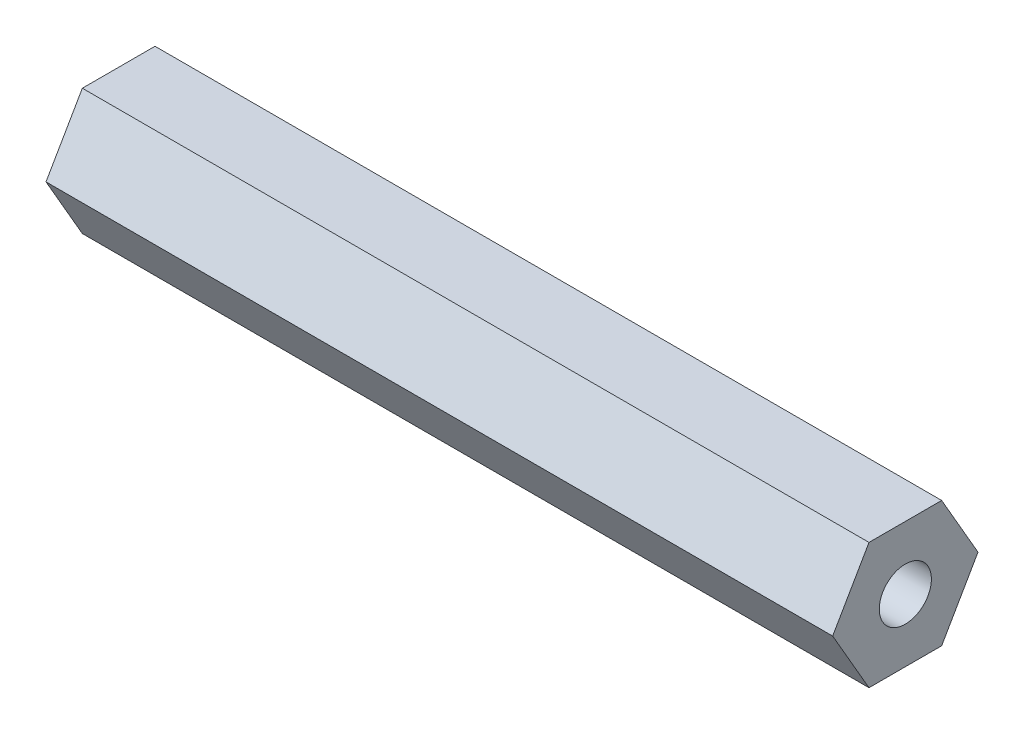
SolidWorks part; units mm, degrees
material "6061-T6 (SS)"
ref_plane "Front Plane" through (0, 0, 0) normal (0, 0, 1) x (1, 0, 0)
ref_plane "Top Plane" through (0, 0, 0) normal (0, 1, 0) x (1, 0, 0)
ref_plane "Right Plane" through (0, 0, 0) normal (1, 0, 0) x (0, 0, -1)
sketch "Sketch1" plane through (0, 0, 0) normal (1, 0, 0) x (0, 0, -1)
  line L1 (3.6662, 6.35) -> (-3.6662, 6.35)
  line L2 (-3.6662, 6.35) -> (-7.3323, 0)
  line L3 (-7.3323, 0) -> (-3.6662, -6.35)
  line L4 (-3.6662, -6.35) -> (3.6662, -6.35)
  line L5 (3.6662, -6.35) -> (7.3323, 0)
  line L6 (7.3323, 0) -> (3.6662, 6.35)
  circle A0 centre (0, 0) radius 6.35 construction
  circle A1 centre (0, 0) radius 2.6289
  dimension "D1" = 5.2578
  dimension "D2" = 12.7
extrude "Boss-Extrude1" add sketch "Sketch1" along normal blind 79.375
